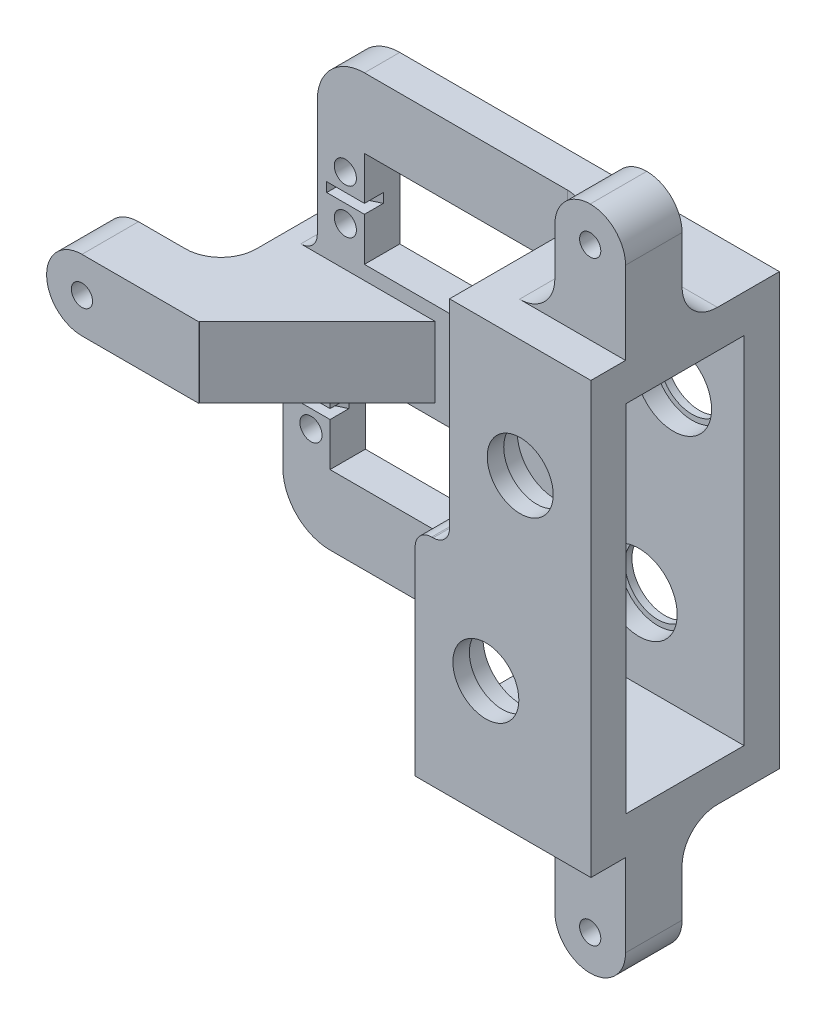
SolidWorks part; units mm, degrees
ref_plane "Front Plane" through (0, 0, 0) normal (0, 0, 1) x (1, 0, 0)
ref_plane "Top Plane" through (0, 0, 0) normal (0, 1, 0) x (1, 0, 0)
ref_plane "Right Plane" through (0, 0, 0) normal (1, 0, 0) x (0, 0, -1)
sketch "Sketch1" plane through (0, 0, 0) normal (0, 0, 1) x (1, 0, 0)
  line L0 (-15, 0) -> (22.2932, 0)
  line L5 (-15, 91.3619) -> (22.2932, 91.3619)
  line L6 (-15, 0) -> (-15, 91.3619)
  line L7 (22.2932, 0) -> (22.2932, 91.3619)
  line L8 (0, 25) -> (7.2932, 66.3619) construction
  line L9 (0, 25) -> (0, 79.2) construction
  circle A1 centre (0, 25) radius 8.1
  circle A2 centre (7.2932, 66.3619) radius 8.1
  point P4 (0, 0)
  dimension "D2" = 16.2
  dimension "D5" = 25
  dimension "D4" = 15
  dimension "D6" = 25
  dimension "D8" = 42
  dimension "D9" = 10
  dimension "D10" = 15
extrude "Boss-Extrude1" add sketch "Sketch1" along normal blind 40
ref_plane "INNER WALL" through (0, 0, 39) normal (0, 0, 1) x (1, 0, 0)
ref_plane "OUTER WALL" through (0, 0, 32.65) normal (0, 0, 1) x (1, 0, 0)
sketch "Sketch2" plane through (0, 0, 0) normal (0, 1, 0) x (1, 0, 0)
  line L1 (-15, -7.5) -> (22.2932, -7.5)
  line L2 (-15, -7.5) -> (-15, -32.5)
  line L3 (-15, -32.5) -> (22.2932, -32.5)
  line L4 (22.2932, -7.5) -> (22.2932, -32.5)
  line L6 (-15, -40) -> (-15, 0) construction
  line L7 (22.2932, -40) -> (22.2932, 0) construction
  point P9 (22.2932, -20)
  point P10 (22.2932, -20)
  dimension "D1" = 25
extrude "Cut-Extrude1" cut sketch "Sketch2" along normal through all from offset 8
sketch "Sketch10" plane through (0, 0, 40) normal (0, 0, 1) x (1, 0, 0)
  circle A0 centre (7.2932, 66.3619) radius 8.1
  circle A1 centre (0, 25) radius 10.837
  circle A2 centre (7.2932, 66.3619) radius 7
  circle A3 centre (0, 25) radius 7
  circle A4 centre (7.2932, 66.3619) radius 8.1 construction
  circle A5 centre (0, 25) radius 8.1 construction
  dimension "D2" = 14
  dimension "D4" = 14
extrude "Boss-Extrude2" add sketch "Sketch10" against normal offset from surface (3.5 mm away) 4 up to face at (-8.1, 25, 32.5)
sketch "Sketch11" plane through (0, 0, 0) normal (0, 0, -1) x (-1, 0, 0)
  circle A0 centre (-7.2932, 66.3619) radius 8.1
  circle A1 centre (-7.2932, 66.3619) radius 7
  circle A2 centre (0, 25) radius 8.1
  circle A3 centre (0, 25) radius 7
  circle A4 centre (0, 25) radius 8.1 construction
  circle A5 centre (-7.2932, 66.3619) radius 8.1 construction
  dimension "D1" = 14
  dimension "D2" = 14
extrude "Boss-Extrude3" add sketch "Sketch11" against normal offset from surface (3.5 mm away) 4 up to face at (8.1, 25, 7.5)
ref_axis "Axis1" through (0, 25, 3.5) along (0, 0, -1)
ref_plane "Plane1" through (0, 25, 0) normal (0, -1, 0) x (-1, 0, 0)
ref_axis "Axis2" through (7.2932, 66.3619, 3.5) along (0, 0, -1)
ref_plane "Plane2" through (0, 66.3619, 0) normal (0, -1, 0) x (-1, 0, 0)
sketch "Sketch12" plane through (0, 0, 0) normal (0, 0, -1) x (-1, 0, 0)
  line L0 (-20.5113, 25) -> (20.5113, 25) construction
  line L1 (15, 0) -> (75.56, 0)
  line L2 (15, 0) -> (15, 91.3619)
  line L3 (15, 91.3619) -> (68.2668, 91.3619)
  line L5 (-20.5113, 66.3619) -> (20.5113, 66.3619) construction
  line L6 (24.66, 35.2) -> (65.56, 35.2)
  line L7 (24.66, 35.2) -> (24.66, 14.8)
  line L8 (24.66, 14.8) -> (65.56, 14.8)
  line L9 (65.56, 35.2) -> (65.56, 14.8)
  line L10 (-22.2932, 91.3619) -> (15, 91.3619) construction
  line L11 (17.3668, 76.5619) -> (58.2668, 76.5619)
  line L12 (17.3668, 76.5619) -> (17.3668, 56.1619)
  line L13 (17.3668, 56.1619) -> (58.2668, 56.1619)
  line L14 (58.2668, 76.5619) -> (58.2668, 56.1619)
  line L16 (15, 0) -> (-22.2932, 0) construction
  line L17 (15, 91.3619) -> (15, 0) construction
  line L18 (68.2668, 91.3619) -> (68.2668, 45.681)
  line L19 (68.2668, 45.681) -> (75.56, 45.681)
  line L20 (75.56, 45.681) -> (75.56, 0)
  line L21 (58.2668, 56.1619) -> (58.2668, 35.2) construction
  line L22 (45.11, 35.2) -> (45.11, 14.8) construction
  line L32 (37.8168, 76.5619) -> (37.8168, 56.1619) construction
  circle A0 centre (35, 25) radius 6.6 construction
  circle A1 centre (0, 25) radius 7 construction
  circle A2 centre (27.7068, 66.3619) radius 6.6 construction
  circle A3 centre (-7.2932, 66.3619) radius 7 construction
  point P15 (45.11, 14.8)
  point P17 (58.2668, 45.681)
  point P27 (17.3668, 66.3619)
  point P34 (37.8168, 56.1619)
  point P53 (45.11, 25)
  dimension "D7" = 13.2
  dimension "D11" = 13.2
  dimension "D2" = 20.4
  dimension "D3" = 40.9
  dimension "D4" = 10.11
  dimension "D9" = 10.11
  dimension "D5" = 35
  dimension "D6" = 10
  dimension "D8" = 10
extrude "Boss-Extrude4" add sketch "Sketch12" against normal up to surface (7.5 mm away) up to face at (8.1, 25, 7.5)
sketch "Sketch13" plane through (0, 0, 0) normal (0, 0, -1) x (-1, 0, 0)
  line L0 (24.66, 35.2) -> (24.66, 14.8) construction
  line L1 (-20.5113, 25) -> (20.5113, 25) construction
  line L2 (65.56, 14.8) -> (65.56, 35.2) construction
  line L3 (17.3668, 76.5619) -> (17.3668, 56.1619) construction
  line L5 (-20.5113, 66.3619) -> (20.5113, 66.3619) construction
  line L6 (58.2668, 56.1619) -> (58.2668, 76.5619) construction
  circle A0 centre (20.61, 29.75) radius 2.3495
  circle A1 centre (20.61, 20.25) radius 2.3495
  circle A2 centre (69.61, 29.75) radius 2.3495
  circle A3 centre (69.61, 20.25) radius 2.3495
  circle A4 centre (13.3168, 71.1119) radius 2.3495
  circle A5 centre (13.3168, 61.6119) radius 2.3495
  circle A6 centre (62.3168, 71.1119) radius 2.3495
  circle A7 centre (62.3168, 61.6119) radius 2.3495
  dimension "D1" = 4.699
  dimension "D2" = 4.05
  dimension "D3" = 9.5
  dimension "D4" = 4.75
  dimension "D5" = 4.05
  dimension "D7" = 9.5
  dimension "D8" = 4.05
  dimension "D9" = 4.75
  dimension "D10" = 4.05
extrude "Cut-Extrude2" cut sketch "Sketch13" against normal up to next
sketch "Sketch22" plane through (0, 0, 7.5) normal (0, 0, 1) x (1, 0, 0)
  line L0 (-58.2668, 56.1619) -> (-58.2668, 76.5619) construction
  line L1 (-58.2668, 65.3619) -> (-66.2668, 65.3619)
  line L2 (-58.2668, 65.3619) -> (-58.2668, 67.3619)
  line L3 (-58.2668, 67.3619) -> (-66.2668, 67.3619)
  line L4 (-66.2668, 65.3619) -> (-66.2668, 67.3619)
  line L5 (-17.3668, 76.5619) -> (-17.3668, 56.1619) construction
  line L6 (-17.3668, 65.3619) -> (-9.3668, 65.3619)
  line L7 (-17.3668, 65.3619) -> (-17.3668, 67.3619)
  line L8 (-17.3668, 67.3619) -> (-9.3668, 67.3619)
  line L9 (-9.3668, 65.3619) -> (-9.3668, 67.3619)
  line L10 (-24.66, 35.2) -> (-24.66, 14.8) construction
  line L11 (-24.66, 24) -> (-16.66, 24)
  line L12 (-24.66, 24) -> (-24.66, 26)
  line L13 (-24.66, 26) -> (-16.66, 26)
  line L14 (-16.66, 24) -> (-16.66, 26)
  line L15 (-65.56, 14.8) -> (-65.56, 35.2) construction
  line L16 (-65.56, 24) -> (-73.56, 24)
  line L17 (-65.56, 24) -> (-65.56, 26)
  line L18 (-65.56, 26) -> (-73.56, 26)
  line L19 (-73.56, 24) -> (-73.56, 26)
  point P24 (-58.2668, 66.3619)
  point P25 (-66.2668, 66.3619)
  point P26 (-73.56, 25)
  point P27 (-65.56, 25)
  dimension "D1" = 2
  dimension "D2" = 8
extrude "Cut-Extrude6" cut sketch "Sketch22" against normal blind 2
sketch "Sketch14" plane through (0, 0, 7.5) normal (0, 0, 1) x (1, 0, 0)
  line L0 (22.2932, 0) -> (22.2932, 91.3619) construction
  line L1 (22.2932, 91.3619) -> (-15, 91.3619)
  line L2 (22.2932, 91.3619) -> (22.2932, 83.3619)
  line L3 (22.2932, 83.3619) -> (-15, 83.3619)
  line L4 (-15, 91.3619) -> (-15, 83.3619)
  line L5 (22.2932, 91.3619) -> (-15, 91.3619) construction
  line L6 (-15, 91.3619) -> (-15, 0) construction
  dimension "D1" = 8
extrude "Boss-Extrude5" add sketch "Sketch14" along normal up to surface (25 mm away) up to face at (-8.1, 25, 32.5)
sketch "Sketch18" plane through (0, 0, 40) normal (0, 0, 1) x (1, 0, 0)
  line L0 (7.2932, 66.3619) -> (7.2932, 25) construction
  line L1 (-15, 91.3619) -> (-7.7068, 91.3619)
  line L2 (-15, 91.3619) -> (-15, 45.681)
  line L3 (-15, 45.681) -> (-7.7068, 45.681)
  line L4 (-7.7068, 91.3619) -> (-7.7068, 45.681)
  line L5 (0, 25) -> (7.2932, 25) construction
  circle A0 centre (7.2932, 66.3619) radius 8.1 construction
  point P13 (7.2932, 45.681)
  dimension "D1" = 15
extrude "Cut-Extrude4" cut sketch "Sketch18" against normal up to surface (32.5 mm away) up to face at (-45.11, 25, 7.5)
sketch "Sketch15" plane through (0, 0, 0) normal (0, 0, -1) x (-1, 0, 0)
  circle A0 centre (0, 25) radius 11
  circle A1 centre (-7.2932, 66.3619) radius 11
  dimension "D1" = 22
extrude "Cut-Extrude3" cut sketch "Sketch15" against normal blind 2
sketch "Sketch19" plane through (0, 0, 32.65) normal (0, 0, 1) x (1, 0, 0)
  line L1 (22.2932, 91.3619) -> (7.2932, 91.3619)
  line L2 (22.2932, 91.3619) -> (22.2932, 116.3619)
  line L3 (22.2932, 116.3619) -> (7.2932, 116.3619)
  line L4 (7.2932, 91.3619) -> (7.2932, 116.3619)
  line L5 (22.2932, 0) -> (7.2932, 0)
  line L6 (22.2932, 0) -> (22.2932, -25)
  line L7 (22.2932, -25) -> (7.2932, -25)
  line L8 (7.2932, 0) -> (7.2932, -25)
  line L9 (-15, 0) -> (22.2932, 0) construction
  dimension "D1" = 15
  dimension "D2" = 25
extrude "Boss-Extrude6" add sketch "Sketch19" against normal blind 12
sketch "Sketch20" plane through (0, 0, 32.65) normal (0, 0, 1) x (1, 0, 0)
  line L0 (-15, 45.681) -> (-7.7068, 45.681) construction
  line L1 (-100.56, 38.181) -> (-68.2668, 38.181)
  line L2 (-100.56, 38.181) -> (-100.56, 53.181)
  line L3 (-100.56, 53.181) -> (-68.2668, 53.181)
  line L4 (-68.2668, 38.181) -> (-68.2668, 53.181)
  line L5 (-75.56, 0) -> (-75.56, 45.681) construction
  line L6 (-68.2668, 45.681) -> (-68.2668, 91.3619) construction
  point P4 (-68.2668, 45.681)
  dimension "D1" = 25
  dimension "D2" = 15
extrude "Boss-Extrude7" add sketch "Sketch20" against normal blind 12 separate body
sketch "Sketch21" plane through (0, 0, 20.65) normal (0, 0, -1) x (-1, 0, 0)
  line L0 (100.56, 38.181) -> (68.2668, 38.181) construction
  line L1 (68.2668, 53.181) -> (75.56, 53.181)
  line L2 (68.2668, 53.181) -> (68.2668, 38.181)
  line L3 (68.2668, 38.181) -> (75.56, 38.181)
  line L4 (75.56, 53.181) -> (75.56, 38.181)
  line L5 (75.56, 0) -> (75.56, 45.681) construction
extrude "Boss-Extrude8" add sketch "Sketch21" along normal up to surface (20.65 mm away) up to face at (-11, 25, 0)
chamfer "Chamfer2" distance 2 angle 65 4 edges at (-65.56, 25, 5.5) (-58.2668, 66.3619, 5.5) (-17.3668, 66.3619, 5.5) (-24.66, 25, 5.5) first distance on face at (-65.56, 25, 5.125) first distance on face at (-58.2668, 66.3619, 5.125) first distance on face at (-17.3668, 66.3619, 5.125) first distance on face at (-24.66, 25, 5.125)
fillet "Fillet1" radius 7.5 13 edges at (-100.56, 53.181, 26.65) (-100.56, 38.181, 26.65) (-75.56, 45.681, 20.65) (7.2932, 116.3619, 26.65) (22.2932, 116.3619, 26.65) (7.2932, -25, 26.65) (22.2932, -25, 26.65) (14.7932, 0, 20.65) (14.7932, 91.3619, 20.65) (7.2932, 0, 26.65) (7.2932, 91.3619, 26.65) (-7.7068, 87.3619, 7.5) (-15, 4, 7.5)
chamfer "Chamfer1" distance 25 angle 45 1 edges at (-68.2668, 45.681, 7.5)
hole_wizard "M4 Clearance Hole1" positions "Sketch23" profile "Sketch24" hole size "M4" standard "ANSI Metric" end condition through all
sketch "Sketch23" plane through (0, 0, 20.65) normal (0, 0, -1) x (-1, 0, 0)
  point P0 (-14.7932, 108.8619)
  point P3 (93.06, 45.681)
  point P6 (-14.7932, -17.5)
sketch "Sketch24" plane through (14.7932, 108.8619, 20.65) normal (1, 0, 0) x (0, 1, 0)
  line L0 (0, 0) -> (0, 19.35)
  line L1 (0, 19.35) -> (2.25, 19.35)
  line L2 (2.25, 19.35) -> (2.25, 0.025)
  line L3 (2.25, 0.025) -> (2.275, 0)
  line L5 (2.275, 0) -> (0, 0)
  line L6 (-2.25, 0.025) -> (-2.275, 0) construction
  line L11 (0, -6.35) -> (0, 107.95) construction
  dimension "Thru Hole Dia." = 4.5
  dimension "Thru Hole Depth" = 19.35
  dimension "Near C'Sink Dia." = 4.55
  dimension "Near C'Sink Angle" = 90
fillet "Fillet2" radius 10 2 edges at (-75.56, 0, 3.75) (-68.2668, 91.3619, 3.75)
fillet "Fillet3" radius 3.5 3 edges at (-15, 45.681, 36.25) (-7.7068, 45.681, 36.25) (-68.2668, 53.181, 3.75)
equation "\"D4@Sketch13\"=\"D3@Sketch13\"/2"
equation "\"D5@Sketch12\"=\"D1@Sketch12\""
equation "\"D8@Sketch13\"=\"D2@Sketch13\""
equation "\"D9@Sketch13\"=\"D7@Sketch13\"/2"
equation "\"D10@Sketch13\"=\"D5@Sketch13\""
